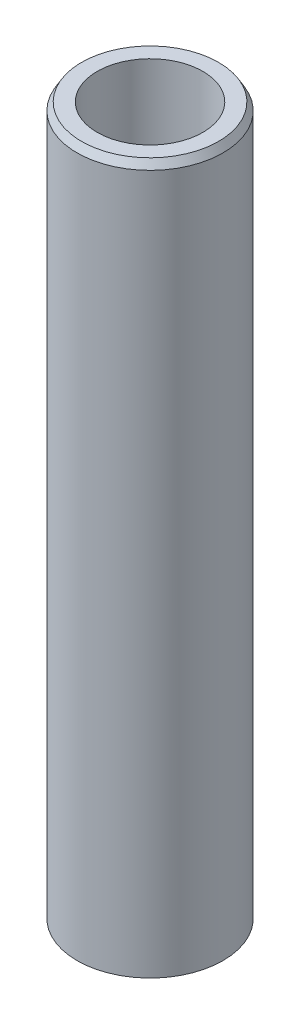
SolidWorks part; units mm, degrees
ref_plane "Front Plane" through (0, 0, 0) normal (0, 0, 1) x (1, 0, 0)
ref_plane "Top Plane" through (0, 0, 0) normal (0, 1, 0) x (1, 0, 0)
ref_plane "Right Plane" through (0, 0, 0) normal (1, 0, 0) x (0, 0, -1)
sketch "Sketch1" plane through (0, 0, 0) normal (0, 1, 0) x (1, 0, 0)
  circle A0 centre (0, 0) radius 15
  dimension "SHAFT_OD" = 30
extrude "Boss-Extrude1" add sketch "Sketch1" along normal blind 146.2946
sketch "Sketch2" plane through (0, 0, 0) normal (0, 1, 0) x (1, 0, 0)
  circle A0 centre (0, 0) radius 10.8677
  dimension "BORE_D" = 21.7353
extrude "Cut-Extrude1" cut sketch "Sketch2" along normal through all
chamfer "Chamfer1" distance 1.5873 angle 30 2 edges at (0, 146.2946, 15) (0, 0, 15) first distance on face at (0, 146.2946, 15) first distance on face at (0, 0, 10.8677)
